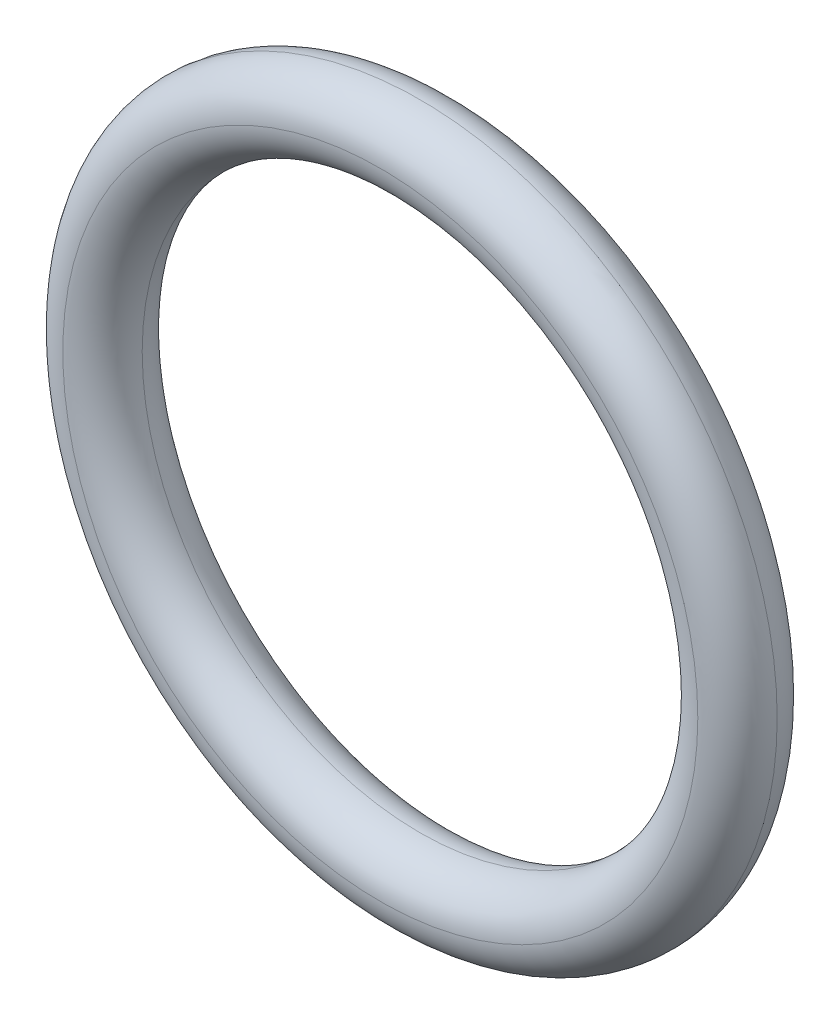
SolidWorks part; units mm, degrees
material "VITON"
ref_plane "Front" through (0, 0, 0) normal (0, 0, 1) x (1, 0, 0)
ref_plane "Top" through (0, 0, 0) normal (0, 1, 0) x (1, 0, 0)
ref_plane "Right" through (0, 0, 0) normal (1, 0, 0) x (0, 0, -1)
sketch "Sketch1" plane through (0, 0, 0) normal (0, 0, 1) x (1, 0, 0)
  circle A0 centre (0, 0) radius 9
extrude "Boss-Extrude1" add sketch "Sketch1" along normal blind 2
sketch "Sketch2" plane through (0, 0, 2) normal (0, 0, 1) x (1, 0, 0)
  circle A0 centre (0, 0) radius 7
extrude "Cut-Extrude1" cut sketch "Sketch2" against normal blind 2
fillet "Fillet1" radius 1 4 edges at (9, 0, 0) (9, 0, 2) (7, 0, 2) (7, 0, 0)
